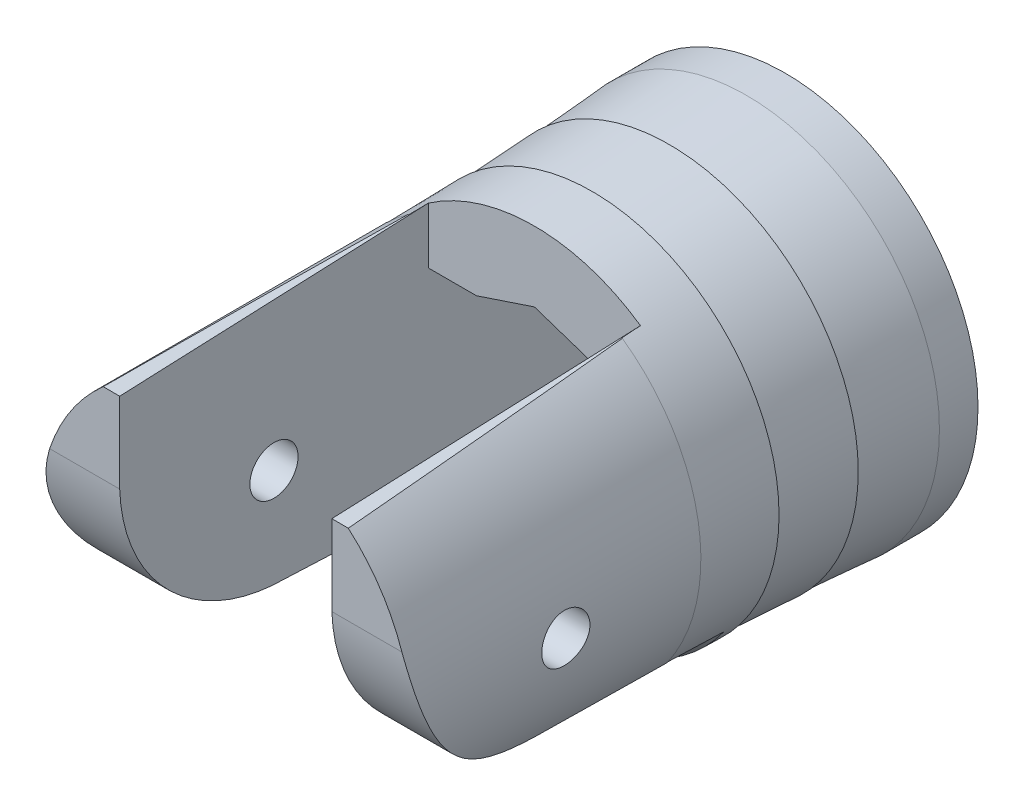
SolidWorks part; units mm, degrees
ref_plane "Front Plane" through (0, 0, 0) normal (0, 0, 1) x (1, 0, 0)
ref_plane "Top Plane" through (0, 0, 0) normal (0, 1, 0) x (1, 0, 0)
ref_plane "Right Plane" through (0, 0, 0) normal (1, 0, 0) x (0, 0, -1)
sketch "Sketch2" plane through (0, 0, 0) normal (0, 0, 1) x (1, 0, 0)
  circle A0 centre (0, 0) radius 10
  dimension "D1" = 20
extrude "Boss-Extrude1" add sketch "Sketch2" along normal blind 2
sketch "Sketch3" plane through (0, 0, 2) normal (0, 0, 1) x (1, 0, 0)
  circle A0 centre (0, 0) radius 10
extrude "Boss-Extrude2" add sketch "Sketch3" along normal blind 4 draft 4
sketch "Sketch4" plane through (0, 0, 6) normal (0, 0, 1) x (1, 0, 0)
  circle A0 centre (0, 0) radius 9.7902
extrude "Boss-Extrude3" add sketch "Sketch4" along normal blind 4 draft 3
sketch "Sketch5" plane through (0, 0, 10) normal (0, 0, 1) x (1, 0, 0)
  circle A0 centre (0, 0) radius 9.6854
extrude "Boss-Extrude4" add sketch "Sketch5" along normal blind 4 draft 1
sketch "Sketch6" plane through (0, 0, 14) normal (0, 0, 1) x (1, 0, 0)
  circle A0 centre (0, 0) radius 9.633
extrude "Boss-Extrude5" add sketch "Sketch6" along normal blind 15
sketch "Sketch7" plane through (0, 0, 0) normal (0, 1, 0) x (1, 0, 0)
  line L0 (0, 3.8556) -> (0, -26.3429) construction
  line L1 (9.633, -13) -> (-9.633, -13) construction
  line L2 (-5.5, -13) -> (5.5, -13)
  line L3 (-5.5, -13) -> (-5.5, -30.8994)
  line L4 (-5.5, -30.8994) -> (5.5, -30.8994)
  line L5 (5.5, -13) -> (5.5, -30.8994)
  dimension "D1" = 11
extrude "Cut-Extrude1" cut sketch "Sketch7" against normal blind 14 and the other way blind 14
sketch "Sketch8" plane through (0, 0, 0) normal (1, 0, 0) x (0, 0, -1)
  line L0 (-13, 9.633) -> (-13, 7.9086)
  line L1 (-13, 7.9086) -> (-29, 7.2408)
  line L2 (-29, 7.9086) -> (-29, -7.9086) construction
  line L3 (-29, 7.2408) -> (-29, 3.0708)
  line L4 (-13, -9.633) -> (-13, -5.5714)
  line L5 (-13, -7.9086) -> (-13, 7.9086) construction
  line L6 (-13, -5.5714) -> (-20.36, -5.2437)
  line L7 (-13, 9.633) -> (-33.7819, 9.633)
  line L8 (-33.7819, 9.633) -> (-33.7819, -9.633)
  line L9 (-33.7819, -9.633) -> (-13, -9.633)
  arc A0 (-29, 3.0708) -> (-20.36, -5.2437) centre (-20.3758, 3.3863) ccw
  dimension "D6" = 8.63
  dimension "D1" = 92.55
  dimension "D2" = 7.36
  dimension "D3" = 92.39
  dimension "D4" = 4.17
  dimension "D5" = 13.48
sketch "Sketch10" plane through (0, 0, 0) normal (0, 0, -1) x (-1, 0, 0)
  line L0 (0, 11.2906) -> (0, -12.202) construction
  line L2 (-5.5, 5) -> (-5.5, -4)
  line L3 (-5.5, -4) -> (5.5, -4)
  line L4 (5.5, 5) -> (5.5, -4)
  line L5 (-5.5, 5) -> (-3, 5)
  line L6 (-3, 5) -> (0, 6)
  line L7 (0, 6) -> (3, 5)
  line L8 (3, 5) -> (5.5, 5)
  dimension "D1" = 11
  dimension "D2" = 2.5
  dimension "D3" = 9
  dimension "D4" = 2.5
  dimension "D5" = 5
  dimension "D6" = 6
extrude "Cut-Extrude4" cut sketch "Sketch10" against normal blind 14
extrude "Cut-Extrude5" cut sketch "Sketch8" against normal blind 10 and the other way blind 10
chamfer "Chamfer1" distance 2 distance2 2 1 edges at (0, -9.633, 13)
sketch "Sketch11" plane through (0, 0, 0) normal (1, 0, 0) x (0, 0, -1)
  line L0 (-13, 9.633) -> (-13, 7.9086) construction
  circle A0 centre (-21, -0.0914) radius 1.25
  dimension "D1" = 2.5
  dimension "D2" = 8
  dimension "D3" = 8
extrude "Cut-Extrude6" cut sketch "Sketch11" against normal blind 10 and the other way blind 10
